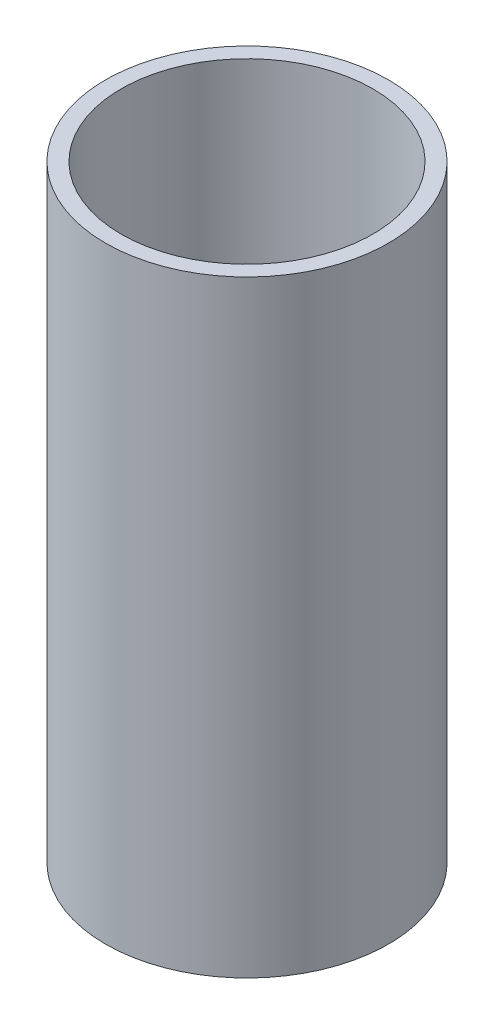
SolidWorks part; units mm, degrees
ref_plane "Front Plane" through (0, 0, 0) normal (0, 0, 1) x (1, 0, 0)
ref_plane "Top Plane" through (0, 0, 0) normal (0, 1, 0) x (1, 0, 0)
ref_plane "Right Plane" through (0, 0, 0) normal (1, 0, 0) x (0, 0, -1)
sketch "Sketch1" plane through (0, 0, 0) normal (0, 1, 0) x (1, 0, 0)
  circle A0 centre (0, 0) radius 55
  dimension "SLEEVE_OD" = 110
extrude "Boss-Extrude1" add sketch "Sketch1" along normal blind 236.0071
sketch "Sketch2" plane through (0, 0, 0) normal (0, 1, 0) x (1, 0, 0)
  circle A0 centre (0, 0) radius 48.9403
  dimension "BORE_D" = 97.8806
extrude "Cut-Extrude1" cut sketch "Sketch2" along normal through all
chamfer "Chamfer1" distance 3.0096 angle 59.477 rebuild error yes
